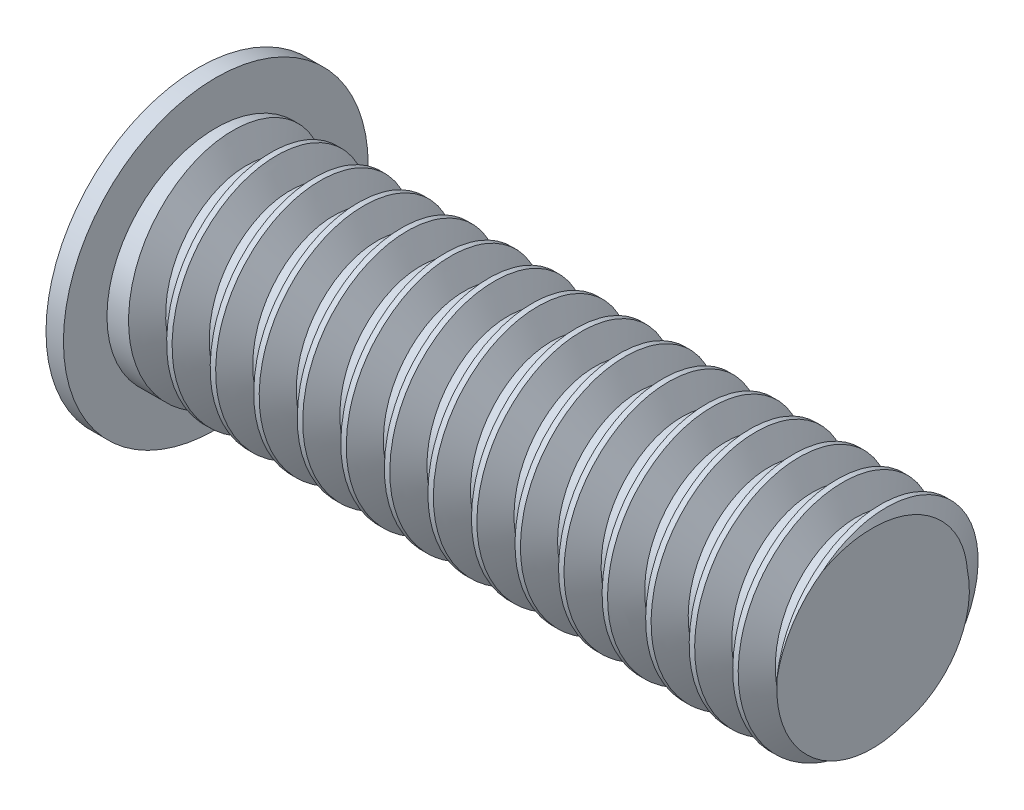
SolidWorks part; units mm, degrees
ref_plane "Front Plane" through (0, 0, 0) normal (0, 0, 1) x (1, 0, 0)
ref_plane "Top Plane" through (0, 0, 0) normal (0, 1, 0) x (1, 0, 0)
ref_plane "Right Plane" through (0, 0, 0) normal (1, 0, 0) x (0, 0, -1)
sketch "Sketch1" plane through (0, 0, 0) normal (0, 1, 0) x (1, 0, 0)
  line L1 (0, 0) -> (-19.49, 0)
  line L2 (0, 0) -> (0, 3.175)
  line L3 (0, 3.175) -> (-19.49, 3.175)
  line L9 (-19.49, -1.27) -> (-19.998, -1.27)
  line L10 (-19.998, -1.27) -> (-19.998, 3.175)
  line L12 (-19.49, 0) -> (-19.49, -1.27)
  line L13 (-19.49, 3.175) -> (-19.998, 3.175)
  dimension "D2" = 3.175
  dimension "D3" = 1.27
revolve "Revolve1" add sketch "Sketch1" angle 360 about L3
sketch "Sketch2" plane through (-19.998, 0, 0) normal (-1, 0, 0) x (0, 0, 1)
  line L2 (-6.1538, 0.3527) -> (0, 0.3527)
  line L3 (0, 0.3527) -> (0, -0.3782)
  line L4 (0, -0.3782) -> (-6.1538, -0.3782)
  line L5 (-6.1538, -0.3782) -> (-6.1538, 0.3527)
extrude "Cut-Extrude1" cut sketch "Sketch2" against normal blind 0.254
thread "Thread1" pitch 1.27 method cut profile "Thread Profile1" start angle 0, offset 0, length 20.16, pitch 1.27, diameter 6.35
ref_plane "Plane1" through (-19.49, 0, -6.35) normal (0, -1, 0) x (0, 0, -1)
sketch "Thread Profile1" plane through (-19.49, 0, -6.35) normal (0, -1, 0) x (0, 0, -1)
  line L0 (0, 0) -> (0, 1.27) construction
  line L11 (0, 0) -> (0, 1.1112)
  line L12 (0, 1.1112) -> (-0.6874, 0.7144)
  line L13 (-0.6874, 0.7144) -> (-0.6874, 0.3969)
  line L15 (-0.6874, 0.3969) -> (0, 0)
  line L17 (-0.6874, 0.5556) -> (0, 0.5556) construction
  point P2 (0, 0)
  dimension "Pitch" = 1.27
  dimension "Profile_Angle" = 60
  dimension "Profile_Land" = 0.3175
  dimension "Profile_Height" = 0.6874
